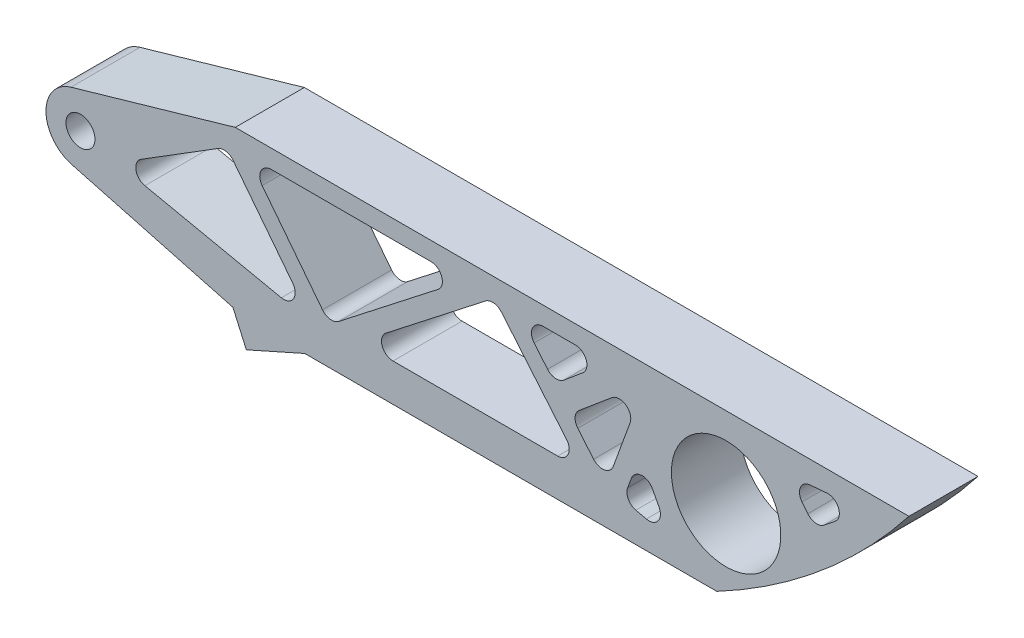
SolidWorks part; units mm, degrees
ref_plane "Front Plane" through (0, 0, 0) normal (0, 0, 1) x (1, 0, 0)
ref_plane "Top Plane" through (0, 0, 0) normal (0, 1, 0) x (1, 0, 0)
ref_plane "Right Plane" through (0, 0, 0) normal (1, 0, 0) x (0, 0, -1)
sketch "Sketch1" plane through (0, 0, 0) normal (0, 0, 1) x (1, 0, 0)
  line L1 (120.65, 22.225) -> (-120.65, 22.225)
  line L2 (120.65, 22.225) -> (120.65, -22.225)
  line L3 (120.65, -22.225) -> (-120.65, -22.225)
  line L4 (-120.65, 22.225) -> (-120.65, -22.225)
  line L5 (120.65, 22.225) -> (-120.65, -22.225) construction
  line L6 (120.65, -22.225) -> (-120.65, 22.225) construction
  point P0 (0, 0)
  dimension "D1" = 241.3
  dimension "D2" = 44.45
extrude "Boss-Extrude1" add sketch "Sketch1" along normal blind 19.06
sketch "Sketch3" plane through (0, 0, 19.06) normal (0, 0, 1) x (1, 0, 0)
  line L0 (0, 0) -> (-120.65, 0) construction
  line L1 (-120.65, 22.225) -> (-120.65, -22.225) construction
  circle A0 centre (-107.95, 0) radius 4
  dimension "D2" = 8
  dimension "D1" = 12.7
extrude "Cut-Extrude1" cut sketch "Sketch3" against normal through all
sketch "Sketch5" plane through (0, 0, 19.06) normal (0, 0, 1) x (1, 0, 0)
  line L0 (-120.65, -22.225) -> (120.65, -22.225) construction
  line L1 (-110.4107, -9.2017) -> (-61.7102, -22.225)
  line L2 (-110.5883, 9.1523) -> (-65.2393, 22.225)
  line L3 (120.65, 22.225) -> (-120.65, 22.225) construction
  line L4 (-65.2393, 22.225) -> (-120.65, 22.225)
  line L5 (-120.65, 22.225) -> (-120.65, -22.225)
  line L6 (-120.65, -22.225) -> (-61.7102, -22.225)
  line L7 (120.65, 22.225) -> (120.65, -22.225)
  line L8 (120.65, -22.225) -> (67.6371, -22.225)
  arc A0 (67.6371, -22.225) -> (120.65, 22.225) centre (-9.5799, 123.7049) ccw
  arc A2 (-110.5883, 9.1523) -> (-110.4107, -9.2017) centre (-107.95, 0) ccw
  line M3 (-120.65, 22.225) -> (-120.65, -22.225)
  line M4 (-120.65, -22.225) -> (120.65, -22.225)
  line M5 (120.65, -22.225) -> (120.65, 22.225)
  line M6 (120.65, 22.225) -> (-120.65, 22.225)
  dimension "D1" = 165.1
  dimension "D2" = 19.05
extrude "Cut-Extrude2" cut sketch "Sketch5" against normal through all contours A0 L8 M5 | A2 L2 L1 M6 M3 M4 region at (-86.2512, -16.4265, 19.06) region at (104.3043, -8.4634, 19.06)
sketch "Sketch6" plane through (0, 0, 19.06) normal (0, 0, 1) x (1, 0, 0)
  line L0 (-107.95, 0) -> (99.7595, 0) construction
  arc A0 (67.6371, -22.225) -> (120.65, 22.225) centre (-9.5799, 123.7049) ccw construction
  circle A1 centre (19.05, 0) radius 3.1347
  dimension "D1" = 127
sketch "Sketch7" plane through (0, 0, 0) normal (0, 0, -1) x (-1, 0, 0)
  line L0 (44.0204, -2.9977) -> (44.0204, 16.0523) construction
  point P3 (44.0204, -2.9977)
  point P4 (44.0204, 16.0523)
  dimension "D1" = 19.05
sketch "Sketch11" plane through (0, 0, 0) normal (0, 0, -1) x (-1, 0, 0)
  line L1 (107.95, 0) -> (-99.7595, 0) construction
  circle A1 centre (-70.2, 0) radius 15.09
  circle A2 centre (107.95, 0) radius 4 construction
  dimension "D1" = 30.18
  dimension "D2" = 178.15
extrude "Cut-Extrude3" cut sketch "Sketch11" against normal through all
sketch "Sketch12" plane through (0, 0, 0) normal (0, 0, -1) x (-1, 0, 0)
  line L3 (62.1778, -29.4105) -> (46.0432, -22.2176)
  line L5 (46.0432, -22.2176) -> (70.9328, -9.772)
  line L6 (70.9328, -9.772) -> (62.1778, -29.4105)
  dimension "D1" = 90
extrude "Boss-Extrude2" add sketch "Sketch12" against normal up to surface (19.06 mm away) up to face at (55.11, 0, 19.06)
sketch "Sketch13" plane through (0, 0, 0) normal (0, 0, -1) x (-1, 0, 0)
  line L0 (-91.178, 12.065) -> (-97.8581, 12.065)
  line L1 (13.9845, -12.065) -> (55.3578, -12.065)
  line L3 (2.0742, -12.065) -> (2.0742, 12.065)
  line L5 (13.9845, -12.065) -> (13.9845, 12.065)
  line L6 (2.0742, 12.065) -> (-49.222, 12.065)
  line L7 (104.3034, 0.0097) -> (58.7357, -5.958)
  line L14 (63.8041, 12.065) -> (-97.8581, 12.065)
  line L15 (-65.0721, -12.065) -> (48.222, -12.065)
  line L16 (58.5717, -12.5473) -> (105.5778, 0.023)
  line L17 (48.222, -12.065) -> (57.0351, -15.994)
  line L18 (57.0351, -15.994) -> (58.5717, -12.5473)
  line L20 (105.5778, 0.023) -> (63.8041, 12.065)
  line L21 (63.8041, 12.065) -> (13.9845, 12.065)
  line L22 (-49.222, -12.065) -> (2.0742, -12.065)
  line L23 (58.5717, -12.5473) -> (105.5778, 0.023)
  line L27 (105.5778, 0.023) -> (63.8041, 12.065)
  arc A0 (-91.178, 12.065) -> (-93.1394, 7.7086) centre (-70.2, 0) ccw
  arc A2 (-49.222, -12.065) -> (-49.222, 12.065) centre (-70.2, 0) ccw
  arc A4 (-97.8581, 12.065) -> (-65.0721, -12.065) centre (9.5799, 123.7049) ccw
  arc A5 (-97.8581, 12.065) -> (-93.1394, 7.7086) centre (9.5799, 123.7049) ccw
  dimension "D1" = 10.16
extrude "Cut-Extrude4" [suppressed] cut sketch "Sketch13" against normal through all
sketch "Sketch14" plane through (0, 0, 19.06) normal (0, 0, 1) x (1, 0, 0)
  line L0 (87.4273, 15.5587) -> (94.742, 6.4153)
  line L1 (94.742, 6.4153) -> (108.4371, 17.3503)
  line L2 (108.4371, 17.3503) -> (87.4273, 15.5587)
  line L3 (6.2381, 17.145) -> (30.5353, -11.846)
  line L4 (46.5104, -0.2633) -> (41.7978, -13.1718)
  line L5 (30.5353, -11.846) -> (-30.9487, -11.846)
  line L6 (-30.9487, -11.846) -> (6.2381, 17.145)
  line L7 (-2.0242, 17.145) -> (-61.8125, 17.145)
  line L8 (-61.8125, 17.145) -> (-39.211, -11.846)
  line L9 (-39.211, -11.846) -> (-2.0242, 17.145)
  line L10 (-67.5872, 16.2898) -> (-44.0189, -13.9413)
  line L11 (-44.0189, -13.9413) -> (-97.91, -2.5585)
  line L12 (-97.91, -2.5585) -> (-67.5872, 16.2898)
  line L13 (120.65, 22.225) -> (-65.2393, 22.225) construction
  line L14 (12.8663, 17.145) -> (22.9708, 5.0885)
  line L15 (22.9708, 5.0885) -> (37.3564, 17.145)
  line L16 (37.3564, 17.145) -> (12.8663, 17.145)
  line L17 (47.7718, 17.2115) -> (27.2354, 0)
  line L18 (-107.95, 0) -> (99.7595, 0) construction
  line L19 (27.2354, 0) -> (37.1635, -11.846)
  line L20 (37.1635, -11.846) -> (47.7718, 17.2115)
  line L21 (41.7978, -13.1718) -> (54.9817, -16.225)
  line L22 (54.9817, -16.225) -> (46.5104, -0.2633)
  dimension "D1" = 5.2446
  dimension "D2" = 5.08
  dimension "D3" = 5.08
  dimension "D4" = 5.08
  dimension "D5" = 37.8264
  dimension "D6" = 5.08
extrude "Cut-Extrude5" cut sketch "Sketch14" against normal through all
fillet "Fillet1" radius 3.175 21 edges at (-67.5872, 16.2898, 9.53) (-44.0189, -13.9413, 9.53) (-97.91, -2.5585, 9.53) (-61.8125, 17.145, 9.53) (-2.0242, 17.145, 9.53) (-39.211, -11.846, 9.53) (-30.9487, -11.846, 9.53) (6.2381, 17.145, 9.53) (30.5353, -11.846, 9.53) (87.4273, 15.5587, 9.53) (108.4371, 17.3503, 9.53) (94.742, 6.4153, 9.53) (47.7718, 17.2115, 9.53) (22.9708, 5.0885, 9.53) (37.3564, 17.145, 9.53) (12.8663, 17.145, 9.53) (27.2354, 0, 9.53) (37.1635, -11.846, 9.53) (46.5104, -0.2633, 9.53) (54.9817, -16.225, 9.53) (41.7978, -13.1718, 9.53)
